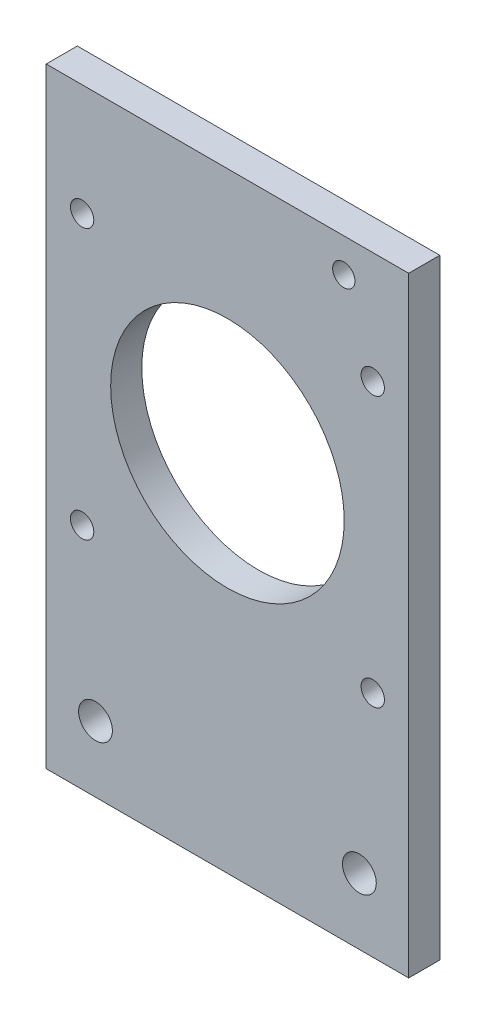
SolidWorks part; units mm, degrees
ref_plane "Front Plane" through (0, 0, 0) normal (0, 0, 1) x (1, 0, 0)
ref_plane "Top Plane" through (0, 0, 0) normal (0, 1, 0) x (1, 0, 0)
ref_plane "Right Plane" through (0, 0, 0) normal (1, 0, 0) x (0, 0, -1)
sketch "Sketch2" plane through (0, 0, 0) normal (0, 0, 1) x (1, 0, 0)
  line L0 (-55, 60.6) -> (55, 60.6) construction
  line L1 (-34.925, 0) -> (34.925, 0)
  line L2 (-34.925, 0) -> (-34.925, 70.1)
  line L3 (-34.925, 70.1) -> (34.925, 70.1) construction
  line L4 (34.925, 0) -> (34.925, 70.1)
  line L5 (0, 60.6) -> (0, 0) construction
  line L6 (0, 60.6) -> (0, 70.1) construction
  line L7 (-34.925, 25.4) -> (34.925, 25.4) construction
  line L10 (34.925, 102.6) -> (-34.925, 102.6) construction
  line L11 (34.925, 70.1) -> (34.925, 102.6)
  line L12 (34.925, 102.6) -> (-34.925, 102.6) construction
  line L13 (-34.925, 102.6) -> (-34.925, 70.1)
  line L14 (34.925, 102.6) -> (34.925, 117.6)
  line L15 (34.925, 117.6) -> (-34.925, 117.6)
  line L16 (-34.925, 102.6) -> (-34.925, 117.6)
  line L17 (-34.925, 25.4) -> (34.925, 25.4) construction
  circle A0 centre (-55, 60.6) radius 3 construction
  circle A1 centre (55, 60.6) radius 3 construction
  circle A2 centre (-55, 60.6) radius 15 construction
  circle A3 centre (55, 60.6) radius 15 construction
  circle A6 centre (0, 70.1) radius 22.5
  circle A7 centre (-55, 60.6) radius 15.6 construction
  point P6 (0, 0)
  dimension "D1" = 6
  dimension "D2" = 30
  dimension "D5" = 45
  dimension "D9" = 15
  dimension "D3" = 110
  dimension "D4" = 9.5
  dimension "D6" = 69.85
  dimension "D7" = 0.6
  dimension "D8" = 32.5
  dimension "D10" = 25.4
  dimension "D12" = 44.7
extrude "Boss-Extrude1" add sketch "Sketch2" along normal mid plane 6
sketch "Sketch3" plane through (0, 0, 3) normal (0, 0, 1) x (1, 0, 0)
  line L0 (34.925, 117.6) -> (-34.925, 117.6) construction
  line L1 (-34.925, 0) -> (-25.425, 0) construction
  line L2 (-34.925, 0) -> (-34.925, 12.7) construction
  line L3 (-34.925, 12.7) -> (-25.425, 12.7) construction
  line L4 (-25.425, 0) -> (-25.425, 12.7) construction
  line L5 (34.925, 0) -> (25.425, 0) construction
  line L6 (34.925, 0) -> (34.925, 12.7) construction
  line L7 (34.925, 12.7) -> (25.425, 12.7) construction
  line L8 (25.425, 0) -> (25.425, 12.7) construction
  line L9 (34.925, 0) -> (34.925, 117.6) construction
  circle A0 centre (-25.425, 12.7) radius 3.2576
  circle A1 centre (25.425, 12.7) radius 3.2576
  circle A4 centre (22.425, 111.1) radius 2.15
  dimension "D1" = 12.7
  dimension "D2" = 6.5151
  dimension "D4" = 12.5
  dimension "D7" = 4.3
  dimension "D3" = 9.5
  dimension "D9" = 6.5
extrude "Cut-Extrude1" cut sketch "Sketch3" against normal blind 6
sketch "Sketch4" plane through (0, 0, 3) normal (0, 0, 1) x (1, 0, 0)
  circle A0 centre (28, 96.1) radius 2.25 construction
  circle A1 centre (-28, 44.1) radius 2.25 construction
  circle A2 centre (28, 44.1) radius 2.25 construction
  circle A3 centre (28, 96.1) radius 2.25
  circle A4 centre (-28, 44.1) radius 2.25
  circle A5 centre (28, 44.1) radius 2.25
  circle A6 centre (-28, 96.1) radius 2.25
extrude "Cut-Extrude2" cut sketch "Sketch4" against normal blind 10
